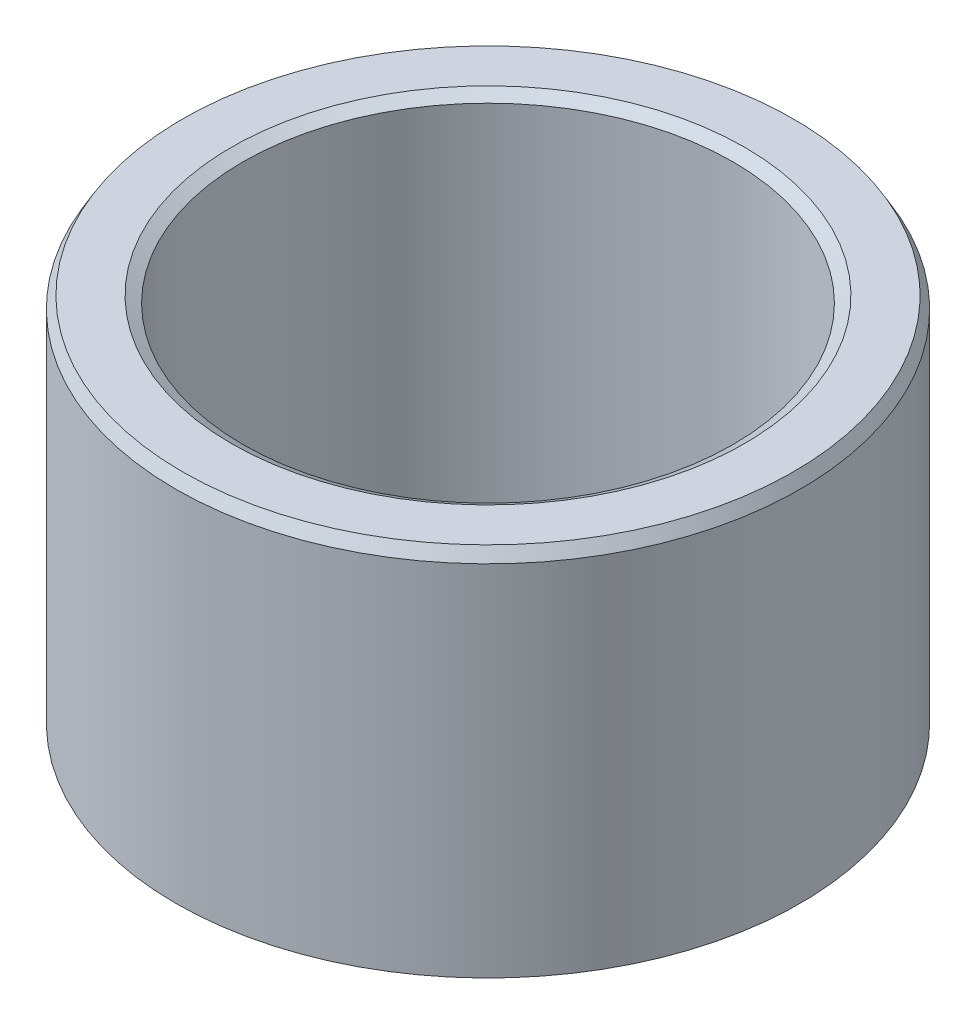
SolidWorks part; units mm, degrees
ref_plane "Front Plane" through (0, 0, 0) normal (0, 0, 1) x (1, 0, 0)
ref_plane "Top Plane" through (0, 0, 0) normal (0, 1, 0) x (1, 0, 0)
ref_plane "Right Plane" through (0, 0, 0) normal (1, 0, 0) x (0, 0, -1)
sketch "Sketch1" plane through (0, 0, 0) normal (0, 1, 0) x (1, 0, 0)
  circle A0 centre (0, 0) radius 60
  dimension "SLEEVE_OD" = 120
extrude "Boss-Extrude1" add sketch "Sketch1" along normal blind 72.452
sketch "Sketch2" plane through (0, 0, 0) normal (0, 1, 0) x (1, 0, 0)
  circle A0 centre (0, 0) radius 47.063
  dimension "BORE_D" = 94.1261
extrude "Cut-Extrude1" cut sketch "Sketch2" along normal through all
chamfer "Chamfer1" distance 2.2451 angle 30 4 edges at (0, 72.452, 47.063) (0, 0, 47.063) (0, 0, 60) (0, 72.452, 60) first distance on face at (0, 72.452, 47.063) first distance on face at (0, 0, 47.063) first distance on face at (0, 72.452, 60)
